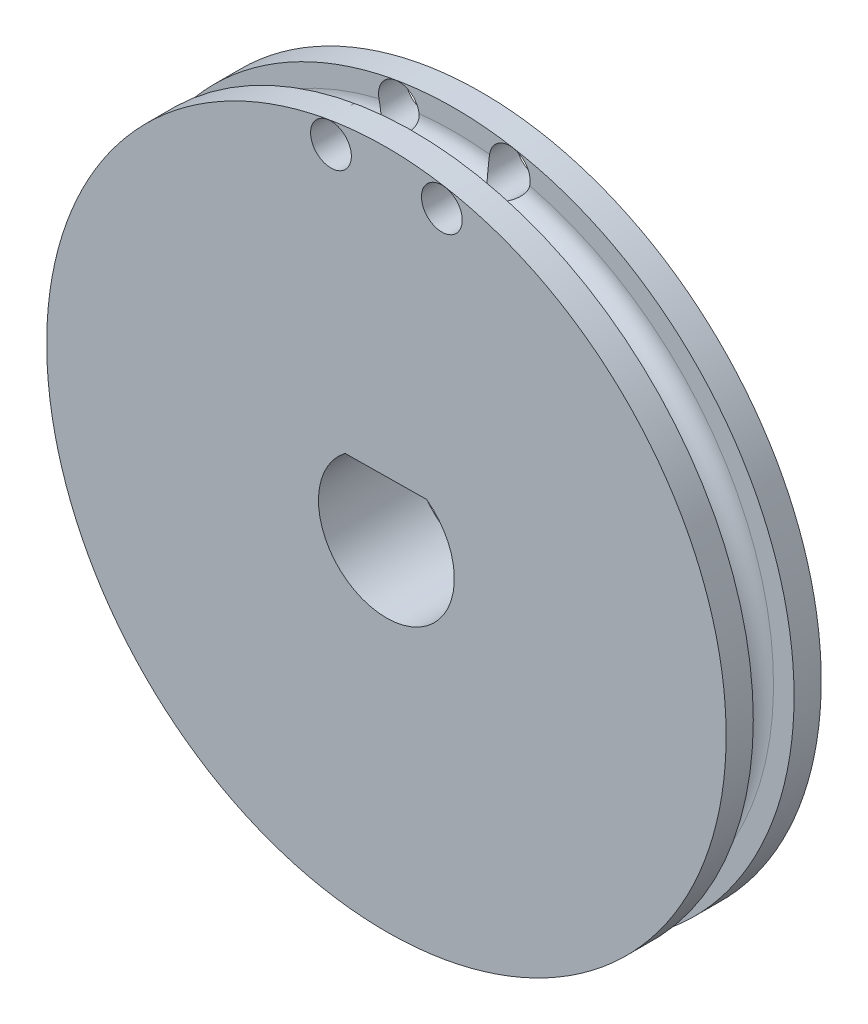
SolidWorks part; units mm, degrees
material "Acrylic (Medium-high impact)"
ref_plane "Front Plane" through (0, 0, 0) normal (0, 0, 1) x (1, 0, 0)
ref_plane "Top Plane" through (0, 0, 0) normal (0, 1, 0) x (1, 0, 0)
ref_plane "Right Plane" through (0, 0, 0) normal (1, 0, 0) x (0, 0, -1)
sketch "Sketch2" plane through (0, 0, 0) normal (1, 0, 0) x (0, 0, -1)
  line L0 (-3.572, 0) -> (3.428, 0)
  line L1 (0, 20.2833) -> (0, -16.4952) construction
  line L2 (-3.572, 0) -> (-3.572, 25)
  line L3 (3.428, 0) -> (3.428, 25)
  line L4 (-3.572, 25) -> (-1.572, 25)
  line L5 (3.428, 25) -> (1.428, 25)
  line L6 (-1.572, 25) -> (-1.572, 23.49)
  line L7 (1.428, 23.49) -> (1.428, 25)
  arc A1 (-1.572, 23.49) -> (1.428, 23.49) centre (-0.072, 23.49) ccw
  dimension "D1" = 7
  dimension "D2" = 25
  dimension "D3" = 2
  dimension "D4" = 2
  dimension "D5" = 25
  dimension "D6" = 1.51
  dimension "D7" = 1.51
revolve "Revolve1" add sketch "Sketch2" angle 360 about L0
sketch "Sketch3" plane through (0, 0, -3.428) normal (0, 0, -1) x (-1, 0, 0)
  line L0 (0, 0) -> (0, 7.3583) construction
  line L1 (-10.3695, 4.1123) -> (10.8046, 3.8835) construction
  line L2 (-2.9566, 4.0322) -> (3.043, 3.9674)
  circle A0 centre (0, 0) radius 5 construction
  arc A1 (-2.9566, 4.0322) -> (3.043, 3.9674) centre (0, 0) ccw
  dimension "D2" = 10
  dimension "D1" = 4
extrude "Cut-Extrude1" cut sketch "Sketch3" against normal blind 9
sketch "Sketch4" plane through (0, 0, -3.428) normal (0, 0, -1) x (-1, 0, 0)
  line L0 (-54.9891, 0) -> (59.117, 0) construction
  line L1 (0, 51.6628) -> (0, 0) construction
  line L2 (0, 0) -> (-9.2544, 52.4842) construction
  line L3 (-9.2544, 52.4842) -> (0, 0) construction
  line L4 (0, 0) -> (9.282, 52.6409) construction
  circle A0 centre (-4.079, 23.1331) radius 1.5
  circle A1 centre (4.079, 23.1331) radius 1.5
  circle A3 centre (0, 0) radius 25 construction
  dimension "D3" = 23.49
  dimension "D1" = 10
  dimension "D2" = 10
  dimension "D4" = 23.49
extrude "Cut-Extrude10" cut sketch "Sketch4" against normal blind 33.49
